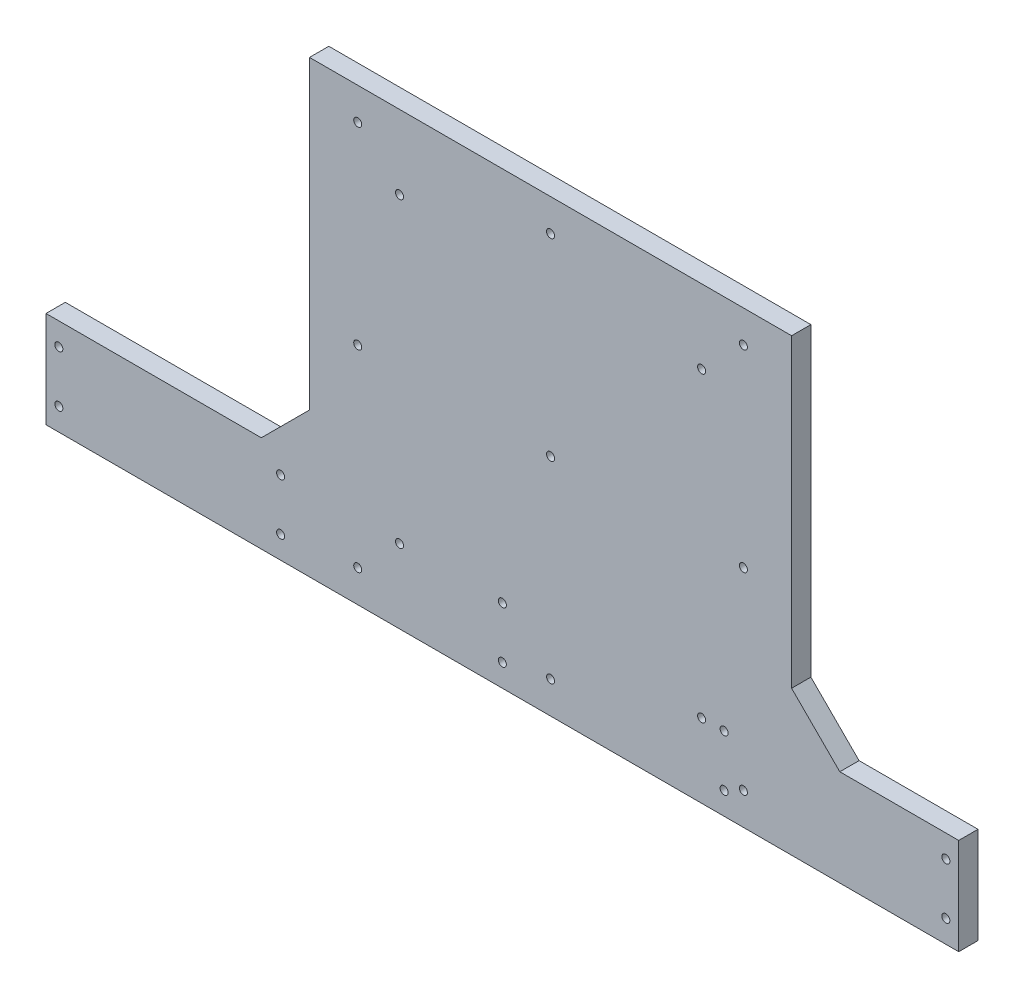
SolidWorks part; units mm, degrees
ref_plane "Plan de face" through (0, 0, 0) normal (0, 0, 1) x (1, 0, 0)
ref_plane "Plan de dessus" through (0, 0, 0) normal (0, 1, 0) x (1, 0, 0)
ref_plane "Plan de droite" through (0, 0, 0) normal (1, 0, 0) x (0, 0, -1)
sketch "Esquisse1" plane through (0, 0, 0) normal (0, 0, 1) x (1, 0, 0)
  line L1 (0, 0) -> (150, 0)
  line L2 (0, 0) -> (0, 140)
  line L3 (0, 140) -> (150, 140)
  line L4 (150, 0) -> (150, 140)
  dimension "D1" = 150
  dimension "D2" = 140
extrude "Boss.-Extru.1" add sketch "Esquisse1" along normal blind 6
sketch "Esquisse2" plane through (0, 0, 6) normal (0, 0, 1) x (1, 0, 0)
  line L0 (75, 0) -> (75, 140) construction
  line L1 (0, 0) -> (150, 0) construction
  line L2 (150, 140) -> (0, 140) construction
  line L3 (75, 70) -> (0, 70) construction
  line L4 (0, 140) -> (0, 0) construction
  circle A0 centre (28, 117) radius 1.25
  circle A1 centre (122, 117) radius 1.25
  circle A2 centre (122, 23) radius 1.25
  circle A3 centre (28, 23) radius 1.25
  dimension "D1" = 94
  dimension "D2" = 94
  dimension "D3" = 2.5
extrude "Enlèv. mat.-Extru.1" cut sketch "Esquisse2" against normal through all
sketch "Esquisse3" plane through (0, 0, 6) normal (0, 0, 1) x (1, 0, 0)
  line L0 (0, 10) -> (150, 10) construction
  line L1 (0, 140) -> (0, 0) construction
  line L2 (150, 0) -> (150, 140) construction
  line L3 (75, 10) -> (75, 140) construction
  line L4 (150, 140) -> (0, 140) construction
  line L5 (0, 70) -> (150, 70) construction
  line L6 (0, 70) -> (150, 10) construction
  line L7 (150, 10) -> (75, 40) construction
  line L8 (75, 40) -> (150, 40) construction
  line L9 (0, 70) -> (150, 70) construction
  circle A0 centre (75, 10) radius 1.25
  circle A1 centre (15, 10) radius 1.25
  circle A2 centre (135, 10) radius 1.25
  circle A3 centre (135, 70) radius 1.25
  circle A4 centre (15, 70) radius 1.25
  circle A5 centre (75, 70) radius 1.25
  circle A6 centre (135, 130) radius 1.25
  circle A7 centre (15, 130) radius 1.25
  circle A8 centre (75, 130) radius 1.25
  dimension "D1" = 2.5
  dimension "D2" = 60
  dimension "D3" = 60
extrude "Enlèv. mat.-Extru.2" cut sketch "Esquisse3" against normal through all
sketch "Esquisse4" plane through (0, 0, 6) normal (0, 0, 1) x (1, 0, 0)
  line L0 (0, 140) -> (0, 0) construction
  line L1 (0, 0) -> (-82, 0)
  line L2 (0, 0) -> (0, 30)
  line L3 (0, 30) -> (-82, 30)
  line L4 (-82, 0) -> (-82, 30)
  line L6 (150, 0) -> (150, 140) construction
  line L7 (150, 0) -> (202, 0)
  line L8 (150, 0) -> (150, 30)
  line L9 (150, 30) -> (202, 30)
  line L10 (202, 0) -> (202, 30)
  dimension "D1" = 82
  dimension "D2" = 30
  dimension "D3" = 52
extrude "Boss.-Extru.2" add sketch "Esquisse4" against normal up to vertex (6 mm away) up to point (0, 140, 0)
sketch "Esquisse5" plane through (0, 0, 6) normal (0, 0, 1) x (1, 0, 0)
  line L0 (-78, 0) -> (-78, 30) construction
  line L1 (-82, 0) -> (202, 0) construction
  line L2 (0, 30) -> (-82, 30) construction
  line L3 (60, 0) -> (60, 30) construction
  line L4 (-78, 15) -> (-82, 15) construction
  line L5 (-82, 30) -> (-82, 0) construction
  line L6 (198, 15) -> (202, 15) construction
  line L7 (198, 0) -> (198, 30) construction
  line L8 (60, 15) -> (-78, 15) construction
  line L9 (-9, 15) -> (-9, 30) construction
  line L10 (60, 15) -> (64, 15) construction
  line L11 (60, 0) -> (60, 30) construction
  line L12 (-9, 15) -> (60, 0) construction
  line L13 (25.5, 7.5) -> (25.5, 15) construction
  line L14 (-9, 0) -> (-9, 30) construction
  line L15 (-9, 15) -> (-13, 15) construction
  line L16 (-9, 0) -> (-9, 30) construction
  line L17 (129, 0) -> (129, 30) construction
  line L18 (129, 15) -> (133, 15) construction
  line L19 (129, 0) -> (129, 30) construction
  line L20 (129, 15) -> (129, 30) construction
  circle A0 centre (-78, 23) radius 1.25
  circle A1 centre (-78, 7) radius 1.25
  circle A2 centre (198, 7) radius 1.25
  circle A3 centre (198, 23) radius 1.25
  circle A4 centre (60, 7) radius 1.25
  circle A5 centre (60, 23) radius 1.25
  circle A6 centre (-9, 23) radius 1.25
  circle A7 centre (-9, 7) radius 1.25
  circle A8 centre (129, 7) radius 1.25
  circle A9 centre (129, 23) radius 1.25
  point P15 (-80, 15)
  dimension "D2" = 2.5
  dimension "D3" = 8
  dimension "D1" = 4
extrude "Enlèv. mat.-Extru.3" cut sketch "Esquisse5" against normal through all
chamfer "Chanfrein1" distance 15 angle 45 2 edges at (0, 30, 3) (150, 30, 3)
